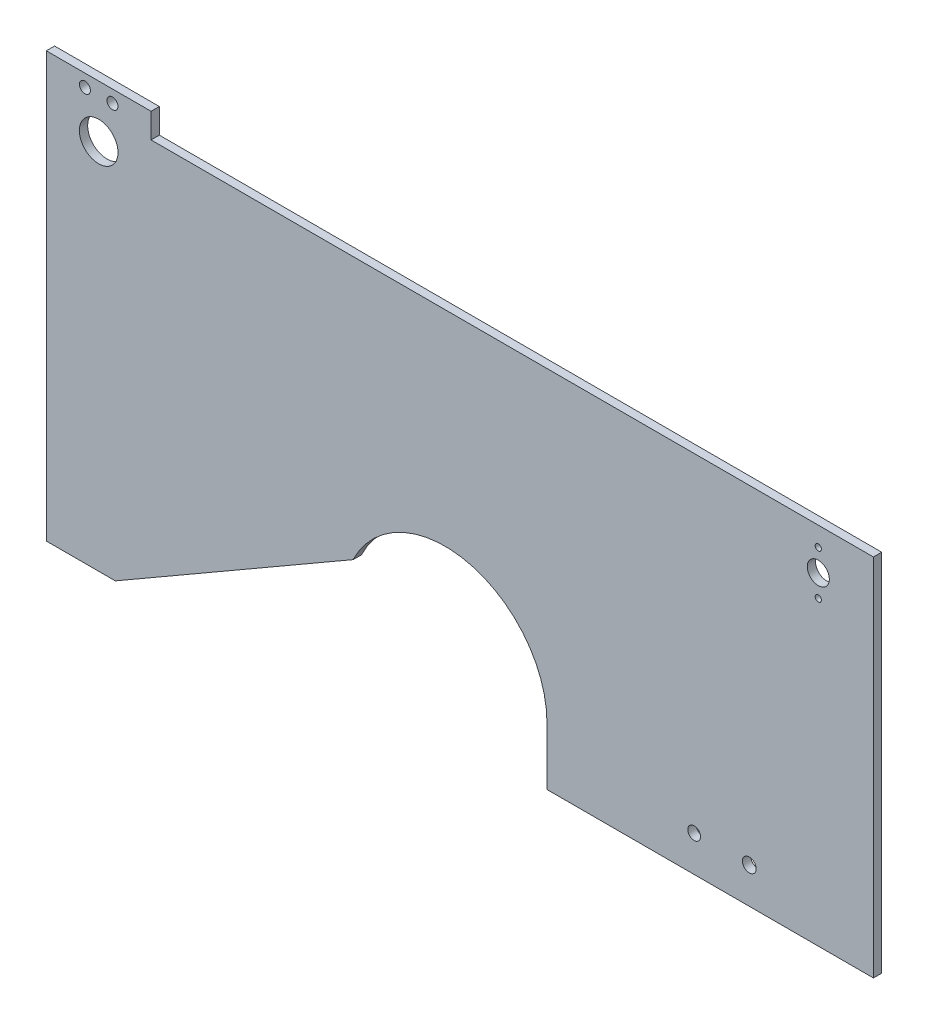
SolidWorks part; units mm, degrees
ref_plane "Front Plane" through (0, 0, 0) normal (0, 0, 1) x (1, 0, 0)
ref_plane "Top Plane" through (0, 0, 0) normal (0, 1, 0) x (1, 0, 0)
ref_plane "Right Plane" through (0, 0, 0) normal (1, 0, 0) x (0, 0, -1)
sketch "Sketch2" plane through (0, 0, 0) normal (0, 0, 1) x (1, 0, 0)
  line L0 (25.0304, 0) -> (111.2865, 49.8)
  line L1 (0, 0) -> (25.0304, 0)
  line L2 (0, 0) -> (0, 154)
  line L4 (300, 0) -> (300, 145)
  line L5 (181.6, 33.7) -> (181.6, 0)
  line L6 (181.6, 0) -> (300, 0)
  line L7 (19, 135) -> (19, 164.3674) construction
  line L11 (38, 145) -> (300, 145)
  line L12 (0, 154) -> (19, 154)
  line L13 (19, 154) -> (38, 154)
  line L14 (38, 154) -> (38, 145)
  line L15 (19, 135) -> (50019, 135) construction
  line L20 (19, 135) -> (19, -49865) construction
  circle A0 centre (19, 135) radius 7
  arc A1 (181.6, 33.7) -> (111.2865, 49.8) centre (144.6, 33.7) ccw
  circle A2 centre (14, 149.5) radius 2
  circle A3 centre (24, 149.5) radius 2
  point P19 (19, 154)
  dimension "D3" = 135
  dimension "D4" = 19
  dimension "D5" = 14
  dimension "D6" = 74
  dimension "D7" = 155.4
  dimension "D8" = 33.7
  dimension "D13" = 4
  dimension "D14" = 5
  dimension "D15" = 14.5
  dimension "D1" = 300
  dimension "D2" = 154
  dimension "D9" = 30
  dimension "D10" = 99.6
  dimension "D11" = 19
  dimension "D12" = 145
  dimension "D16" = 9
extrude "Boss-Extrude2" add sketch "Sketch2" along normal blind 3
sketch "Sketch3" plane through (0, 0, 3) normal (0, 0, 1) x (1, 0, 0)
  line L0 (300, 0) -> (300, 145) construction
  line L1 (181.6, 0) -> (300, 0)
  line L2 (181.6, 0) -> (181.6, 12.75)
  line L3 (181.6, 12.75) -> (300, 12.75)
  line L4 (300, 0) -> (300, 12.75)
  dimension "D1" = 12.75
extrude "Cut-Extrude1" cut sketch "Sketch3" against normal through all
sketch "Sketch4" plane through (0, 0, 3) normal (0, 0, 1) x (1, 0, 0)
  line L0 (19, 135) -> (19, -49865) construction
  line L1 (19, 135) -> (-49981, 135) construction
sketch "Sketch5" plane through (0, 0, 3) normal (0, 0, 1) x (1, 0, 0)
  line L0 (300, 12.75) -> (300, 145) construction
  line L1 (300, 12.75) -> (181.6, 12.75) construction
  line L2 (300, 145) -> (38, 145) construction
  circle A0 centre (254.98, 25.75) radius 2.5
  circle A1 centre (234.98, 25.75) radius 2.3061
  circle A2 centre (280, 130) radius 4
  circle A3 centre (280, 138) radius 1.125
  circle A4 centre (280, 122) radius 1.125
  dimension "D1" = 45.02
  dimension "D2" = 13
  dimension "D3" = 20
  dimension "D4" = 13
  dimension "D5" = 4.6121
  dimension "D6" = 5
  dimension "D7" = 8
  dimension "D8" = 15
  dimension "D9" = 2.25
  dimension "D10" = 8
  dimension "D11" = 8
  dimension "D12" = 2.25
  dimension "D13" = 20
  dimension "D14" = 20
  dimension "D15" = 20
extrude "Cut-Extrude2" cut sketch "Sketch5" against normal through all
